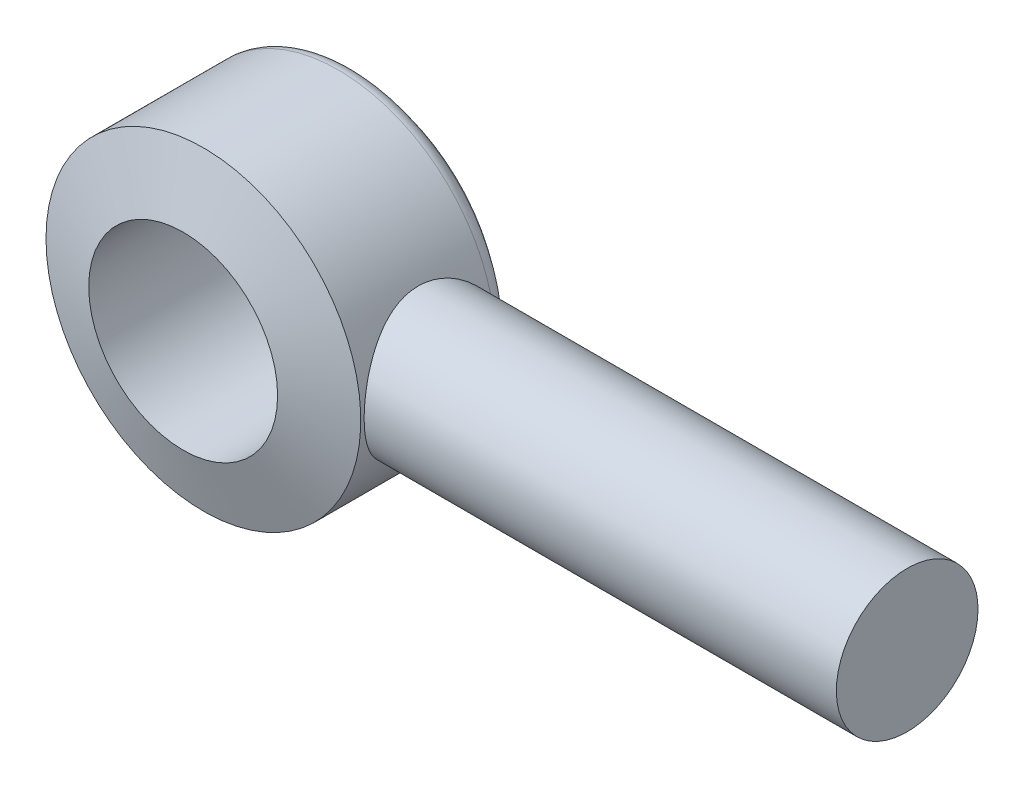
SolidWorks part; units mm, degrees
ref_plane "Front Plane" through (0, 0, 0) normal (0, 0, 1) x (1, 0, 0)
ref_plane "Top Plane" through (0, 0, 0) normal (0, 1, 0) x (1, 0, 0)
ref_plane "Right Plane" through (0, 0, 0) normal (1, 0, 0) x (0, 0, -1)
sketch "Sketch2" plane through (0, 0, 0) normal (0, 1, 0) x (1, 0, 0)
  line L0 (0, 10) -> (0, -12) construction
  line L1 (0, -12) -> (20, -12) construction
  line L2 (20, -12) -> (20, 7.7088)
  line L3 (19.2189, 9.2944) -> (17.539, 10.5857)
  line L4 (16.3202, 11) -> (12, 11)
  line L5 (0, 10) -> (12, 10)
  line L6 (12, 10) -> (12, 11)
  line L7 (12, -12) -> (12, 7.4973)
  line L8 (12, 7.4973) -> (0, 7.4973)
  line L9 (12, -12) -> (20, -12)
  line L10 (0, 10) -> (0, 7.4973)
  line L11 (0, 10) -> (0, 7.4973)
  line L12 (12, -12) -> (20, -9.4302)
  arc A0 (20, 7.7088) -> (19.2189, 9.2944) centre (18, 7.7088) ccw
  arc A1 (17.539, 10.5857) -> (16.3202, 11) centre (16.3202, 9) ccw
  point P15 (17, 11)
  dimension "D7" = 2
  dimension "D1" = 10
  dimension "D2" = 12
  dimension "D3" = 20
  dimension "D4" = 12
  dimension "D5" = 5
  dimension "D6" = 1
revolve "Revolve1" add sketch "Sketch2" angle 360 about L0 region at (14.3759, 0, -1.2401)
sketch3d "3DSketch1"
  line L0 (0, 0, 0) -> (80, 0, 0) construction
  circle A0 centre (80, 0, 0) radius 9
  circle A1 centre (80, 0, 0) radius 9
  point P4 (89, 0, 0)
  point P6 (71, 0, 0)
  dimension "D2" = 18
  dimension "D1" = 80
extrude "Boss-Extrude3" add sketch "3DSketch1" along direction (1, 0, 0) on the side against the normal blind 65 contours A0
sketch3d "3DSketch2"
  line L0 (19.5273, -0.0392, -8.9999) -> (80, 0, 0)
  spline S0 degree 3 poles (19.4531, -4.6449, -7.7088) (19.5357, -4.299, -7.9172) (19.5792, -3.9389, -8.1025) (19.6205, -3.1923, -8.4246) (19.6177, -2.8028, -8.5622) (19.5935, -2.0172, -8.7805) (19.5724, -1.6204, -8.8622) (19.5391, -0.818, -8.9719) (19.5274, -0.4125, -8.9999) (19.5273, 0.4079, -9.0001) (19.5391, 0.8159, -8.9721) (19.5724, 1.6191, -8.8624) (19.5934, 2.0157, -8.7808) (19.6176, 2.7997, -8.5631) (19.6205, 3.1897, -8.4257) (19.5793, 3.9384, -8.1028) (19.5357, 4.299, -7.9172) (19.4531, 4.6449, -7.7088) knots 0 0 0 0 0.125 0.125 0.25 0.25 0.375 0.375 0.5 0.5 0.625 0.625 0.75 0.75 0.875 0.875 1 1 1 1 construction
  dimension "D1" = 61.1387
